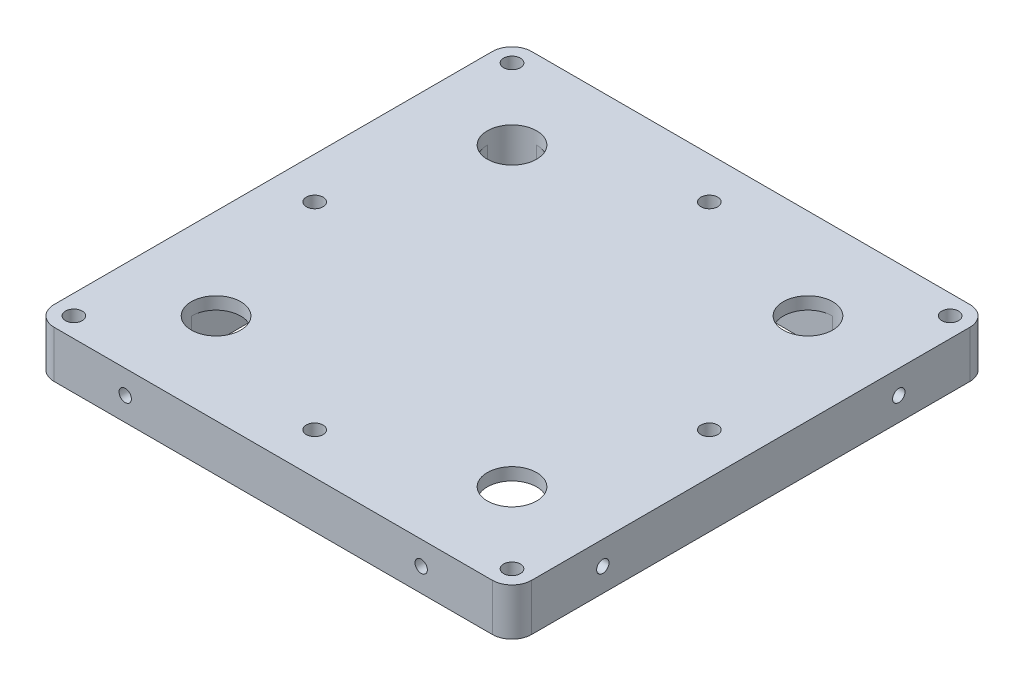
SolidWorks part; units mm, degrees
material "6061-T6 (SS)"
ref_plane "Front Plane" through (0, 0, 0) normal (0, 0, 1) x (1, 0, 0)
ref_plane "Top Plane" through (0, 0, 0) normal (0, 1, 0) x (1, 0, 0)
ref_plane "Right Plane" through (0, 0, 0) normal (1, 0, 0) x (0, 0, -1)
sketch "Sketch1" plane through (0, 0, 0) normal (0, 1, 0) x (1, 0, 0)
  line L1 (48.4125, -48.4125) -> (-48.4125, -48.4125)
  line L2 (48.4125, -48.4125) -> (48.4125, 48.4125)
  line L3 (48.4125, 48.4125) -> (-48.4125, 48.4125)
  line L4 (-48.4125, -48.4125) -> (-48.4125, 48.4125)
  line L5 (48.4125, -48.4125) -> (-48.4125, 48.4125) construction
  line L6 (48.4125, 48.4125) -> (-48.4125, -48.4125) construction
  point P0 (0, 0)
  dimension "D1" = 96.825
extrude "Boss-Extrude1" add sketch "Sketch1" along normal mid plane 9.525
fillet "Fillet1" radius 4 4 edges at (-48.4125, 0, -48.4125) (48.4125, 0, -48.4125) (48.4125, 0, 48.4125) (-48.4125, 0, 48.4125)
sketch "Sketch4" plane through (-48.4125, 0, 0) normal (-1, 0, 0) x (0, 0, 1)
  point P0 (-30, 0)
  point P2 (30, 0)
  dimension "D1" = 30
  dimension "D2" = 30
hole_wizard "M3x0.5 Tapped Hole1" positions "Sketch4" profile "Sketch3" tap size "M3x0.5" standard "ANSI Metric"
sketch "Sketch3" plane through (-48.4125, 0, -30) normal (0, 1, 0) x (0, 0, 1)
  line L0 (0, 0) -> (0, 10.7511)
  line L1 (0, 10.7511) -> (1.25, 10)
  line L2 (1.25, 10) -> (1.25, 0)
  line L5 (1.25, 0) -> (0, 0)
  line L10 (0, 10.7511) -> (-1.25, 10) construction
  line L11 (0, -6.35) -> (0, 107.95) construction
  dimension "Tap Drill Dia." = 2.5
  dimension "Tap Drill Depth" = 10
  dimension "Drill Angle" = 118
sketch "Sketch7" plane through (0, 0, -48.4125) normal (0, 0, -1) x (-1, 0, 0)
  point P0 (-30, 0)
  point P2 (30, 0)
  dimension "D1" = 30
  dimension "D2" = 30
hole_wizard "M3x0.5 Tapped Hole2" positions "Sketch7" profile "Sketch6" tap size "M3x0.5" standard "ANSI Metric"
sketch "Sketch6" plane through (30, 0, -48.4125) normal (1, 0, 0) x (0, 1, 0)
  line L0 (0, 0) -> (0, 10.7511)
  line L1 (0, 10.7511) -> (1.25, 10)
  line L2 (1.25, 10) -> (1.25, 0)
  line L5 (1.25, 0) -> (0, 0)
  line L10 (0, 10.7511) -> (-1.25, 10) construction
  line L11 (0, -6.35) -> (0, 107.95) construction
  dimension "Tap Drill Dia." = 2.5
  dimension "Tap Drill Depth" = 10
  dimension "Drill Angle" = 118
sketch "Sketch10" plane through (0, 4.7625, 0) normal (0, 1, 0) x (1, 0, 0)
  arc A0 (-48.4125, -44.4125) -> (-44.4125, -48.4125) centre (-44.4125, -44.4125) ccw construction
  arc A1 (-44.4125, 48.4125) -> (-48.4125, 44.4125) centre (-44.4125, 44.4125) ccw construction
  arc A2 (48.4125, 44.4125) -> (44.4125, 48.4125) centre (44.4125, 44.4125) ccw construction
  arc A3 (44.4125, -48.4125) -> (48.4125, -44.4125) centre (44.4125, -44.4125) ccw construction
  point P0 (-44.4125, 44.4125)
  point P2 (44.4125, 44.4125)
  point P4 (44.4125, -44.4125)
  point P6 (-44.4125, -44.4125)
hole_wizard "M3 Clearance Hole1" positions "Sketch10" profile "Sketch9" hole size "M3" standard "ANSI Metric" end condition through all
sketch "Sketch9" plane through (-44.4125, 4.7625, -44.4125) normal (1, 0, 0) x (0, 0, 1)
  line L0 (0, 0) -> (0, 9.525)
  line L1 (0, 9.525) -> (1.7, 9.525)
  line L2 (1.7, 9.525) -> (1.7, 0)
  line L5 (1.7, 0) -> (0, 0)
  line L11 (0, -6.35) -> (0, 107.95) construction
  dimension "Thru Hole Dia." = 3.4
  dimension "Thru Hole Depth" = 9.525
sketch "Sketch13" plane through (48.4125, 0, 0) normal (1, 0, 0) x (0, 0, -1)
  point P0 (-30, 0)
  point P2 (30, 0)
  dimension "D1" = 30
  dimension "D2" = 30
hole_wizard "M3x0.5 Tapped Hole3" positions "Sketch13" profile "Sketch12" tap size "M3x0.5" standard "ANSI Metric"
sketch "Sketch12" plane through (48.4125, 0, 30) normal (0, 1, 0) x (0, 0, -1)
  line L0 (0, 0) -> (0, 10.7511)
  line L1 (0, 10.7511) -> (1.25, 10)
  line L2 (1.25, 10) -> (1.25, 0)
  line L5 (1.25, 0) -> (0, 0)
  line L10 (0, 10.7511) -> (-1.25, 10) construction
  line L11 (0, -6.35) -> (0, 107.95) construction
  dimension "Tap Drill Dia." = 2.5
  dimension "Tap Drill Depth" = 10
  dimension "Drill Angle" = 118
sketch "Sketch16" plane through (0, 0, 48.4125) normal (0, 0, 1) x (1, 0, 0)
  point P0 (-30, 0)
  point P2 (30, 0)
  dimension "D1" = 30
  dimension "D2" = 30
hole_wizard "M3x0.5 Tapped Hole4" positions "Sketch16" profile "Sketch15" tap size "M3x0.5" standard "ANSI Metric"
sketch "Sketch15" plane through (-30, 0, 48.4125) normal (1, 0, 0) x (0, -1, 0)
  line L0 (0, 0) -> (0, 10.7511)
  line L1 (0, 10.7511) -> (1.25, 10)
  line L2 (1.25, 10) -> (1.25, 0)
  line L5 (1.25, 0) -> (0, 0)
  line L10 (0, 10.7511) -> (-1.25, 10) construction
  line L11 (0, -6.35) -> (0, 107.95) construction
  dimension "Tap Drill Dia." = 2.5
  dimension "Tap Drill Depth" = 10
  dimension "Drill Angle" = 118
sketch "Sketch19" plane through (0, -4.7625, 0) normal (0, -1, 0) x (-1, 0, 0)
  line L0 (0, 40) -> (0, -40) construction
  line L2 (-40, 0) -> (40, 0) construction
  point P0 (-40, 0)
  point P2 (0, 40)
  point P4 (40, 0)
  point P6 (0, -40)
  point P20 (0, 0)
  point P23 (0, 0)
  dimension "D1" = 40
  dimension "D2" = 40
hole_wizard "CSK for M3 SFHCS1" positions "Sketch19" profile "Sketch18" countersink size "M3" standard "ANSI Metric" end condition through all
sketch "Sketch18" plane through (40, -4.7625, 0) normal (1, 0, 0) x (0, 0, -1)
  line L0 (0, 0) -> (0, 9.525)
  line L1 (0, 9.525) -> (1.7, 9.525)
  line L2 (1.7, 9.525) -> (1.7, 1.66)
  line L3 (1.7, 1.66) -> (3.36, 0)
  line L5 (3.36, 0) -> (0, 0)
  line L6 (-1.7, 1.66) -> (-3.36, 0) construction
  line L11 (0, -6.35) -> (0, 107.95) construction
  dimension "Thru Hole Dia." = 3.4
  dimension "Thru Hole Depth" = 9.525
  dimension "Near C'Sink Dia." = 6.72
  dimension "Near C'Sink Angle" = 90
sketch "Sketch20" plane through (0, -4.7625, 0) normal (0, -1, 0) x (1, 0, 0)
  line L1 (30, -35) -> (-30, -35)
  line L2 (35, -30) -> (35, 30)
  line L3 (30, 35) -> (-30, 35)
  line L4 (-35, -30) -> (-35, 30)
  line L5 (35, -35) -> (-35, 35) construction
  line L6 (35, 35) -> (-35, -35) construction
  arc A0 (-30, -35) -> (-35, -30) centre (-30, -30) cw
  arc A1 (30, -35) -> (35, -30) centre (30, -30) ccw
  arc A2 (35, 30) -> (30, 35) centre (30, 30) ccw
  arc A3 (-30, 35) -> (-35, 30) centre (-30, 30) ccw
  point P0 (0, 0)
  dimension "D3" = 5
  dimension "D1" = 70
  dimension "D2" = 70
extrude "Cut-Extrude1" cut sketch "Sketch20" against normal blind 7
sketch "Sketch21" plane through (0, 2.2375, 0) normal (0, -1, 0) x (1, 0, 0)
  circle A0 centre (-30, 30) radius 5
  circle A1 centre (30, 30) radius 5
  circle A2 centre (30, -30) radius 5
  circle A3 centre (-30, -30) radius 5
  point P12 (0, 0)
  dimension "D1" = 10
  dimension "D2" = 10
  dimension "D3" = 10
  dimension "D4" = 10
extrude "Cut-Extrude2" cut sketch "Sketch21" against normal through all
